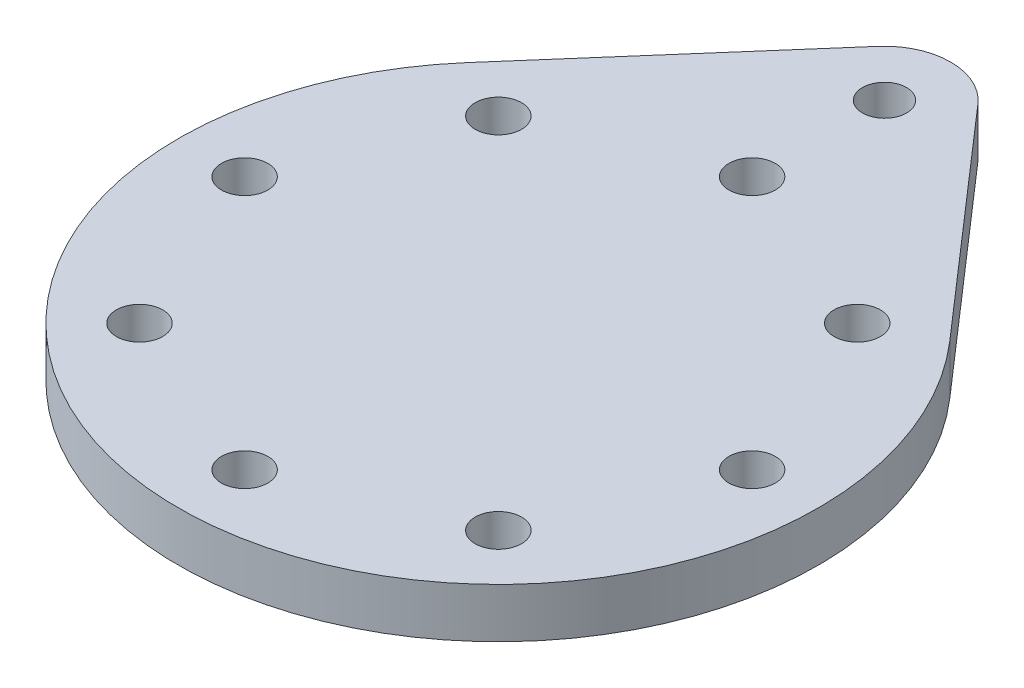
SolidWorks part; units mm, degrees
ref_plane "Front Plane" through (0, 0, 0) normal (0, 0, 1) x (1, 0, 0)
ref_plane "Top Plane" through (0, 0, 0) normal (0, 1, 0) x (1, 0, 0)
ref_plane "Right Plane" through (0, 0, 0) normal (1, 0, 0) x (0, 0, -1)
sketch "Sketch1" plane through (0, 0, 0) normal (0, 1, 0) x (1, 0, 0)
  line L0 (-4.5226, 38.9429) -> (-21.8592, 19.0571)
  line L1 (4.5226, 38.9429) -> (21.8592, 19.0571)
  circle A0 centre (0, 0) radius 35 construction
  circle A1 centre (0, 35) radius 2
  circle A2 centre (0, 35) radius 6
  circle A3 centre (0, 0) radius 23 construction
  circle A4 centre (0, 0) radius 29
  circle A5 centre (0, 23) radius 2.1
  circle A6 centre (16.2635, 16.2635) radius 2.1
  circle A7 centre (23, 0) radius 2.1
  circle A8 centre (16.2635, -16.2635) radius 2.1
  circle A9 centre (0, -23) radius 2.1
  circle A10 centre (-16.2635, -16.2635) radius 2.1
  circle A11 centre (-23, 0) radius 2.1
  circle A12 centre (-16.2635, 16.2635) radius 2.1
  point P26 (0, 0)
  dimension "D1" = 70
  dimension "D2" = 4
  dimension "D3" = 46
  dimension "D4" = 12
  dimension "D5" = 4.2
  dimension "D6" = 8
extrude "Boss-Extrude1" add sketch "Sketch1" along normal blind 4.5 contours A4 A12 A11 A10 A9 A8 A7 A6 A5 | A4 L1 A2 | A4 A2 L0 | A2 A1 region at (-9.3787, 0, -29.7863) region at (0, 0, -40.8303) region at (0, 0, 0) region at (9.3787, 0, -29.7863)
